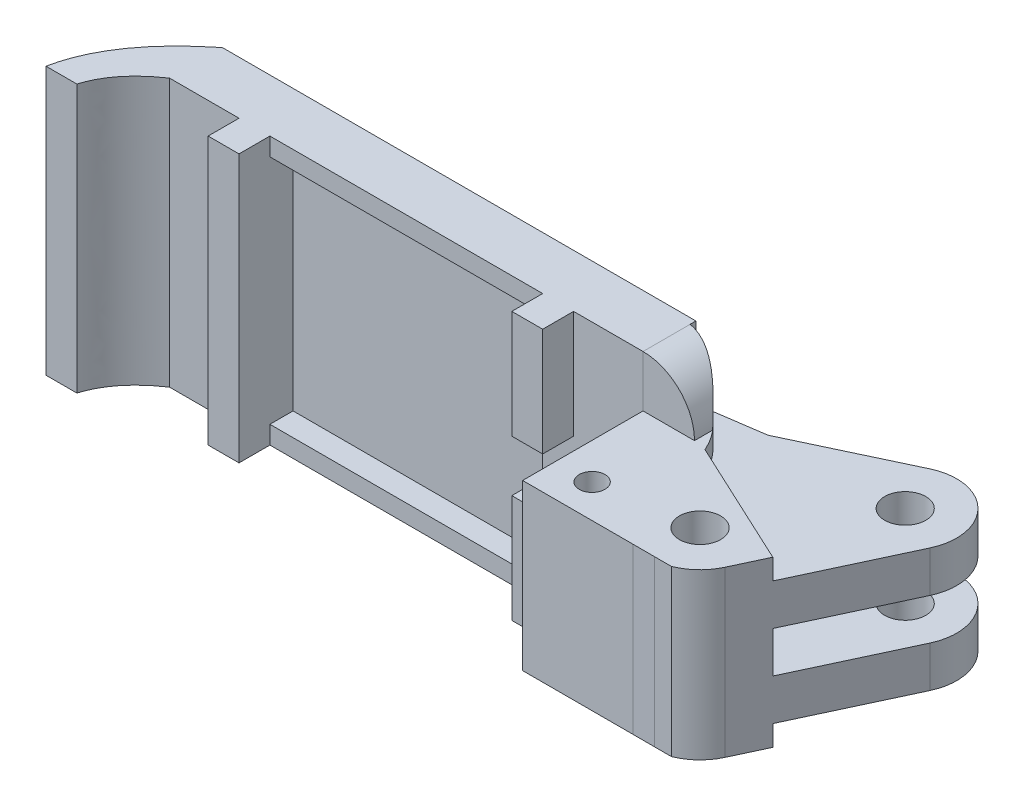
SolidWorks part; units mm, degrees
ref_plane "Front Plane" through (0, 0, 0) normal (0, 0, 1) x (1, 0, 0)
ref_plane "Top Plane" through (0, 0, 0) normal (0, 1, 0) x (1, 0, 0)
ref_plane "Right Plane" through (0, 0, 0) normal (1, 0, 0) x (0, 0, -1)
sketch "Sketch2" plane through (0, 0, 0) normal (0, 1, 0) x (1, 0, 0)
  line L0 (-8.5236, 1.406) -> (-14.8628, -12.1887)
  line L1 (-15.1825, 8.0439) -> (-25.8895, 3.0099)
  line L2 (-19.187, -14.7177) -> (-17.5368, -14.7177)
  line L3 (-19.187, -14.7177) -> (-21.2638, -14.713)
  line L4 (-25.8895, 3.0099) -> (-31.9894, 2.1239)
  line L5 (-31.9894, 2.1239) -> (-31.9894, 1.5541)
  line L6 (-31.9894, -14.713) -> (-21.2638, -14.713)
  arc A0 (-8.5236, 1.406) -> (-15.1825, 8.0439) centre (-13.0551, 3.519) ccw
  circle A1 centre (-19.3944, -10.0756) radius 2
  arc A2 (-17.5368, -14.7177) -> (-14.8628, -12.1887) centre (-19.3944, -10.0756) ccw
  arc A3 (-31.9894, -14.713) -> (-31.9894, 1.5541) centre (-33.2584, -6.5794) ccw
  circle A4 centre (-13.0551, 3.519) radius 2
  dimension "D1" = 15
extrude "Boss-Extrude1" add sketch "Sketch2" along normal blind 8 and the other way blind 8
sketch "Sketch3" plane through (0, -8, 0) normal (0, -1, 0) x (1, 0, 0)
  line L0 (-13.3837, 9.0166) -> (-36.0192, -1.5385)
  line L1 (-14.8628, 12.1887) -> (-8.5236, -1.406) construction
  line L3 (-25.8895, -3.0099) -> (-31.9894, -2.1239) construction
  line L4 (-15.1825, -8.0439) -> (-25.8895, -3.0099) construction
  line L5 (-25.8895, -3.0099) -> (-36.0192, -1.5385)
  line L6 (-15.1825, -8.0439) -> (-25.8895, -3.0099)
  line L7 (-13.3837, 9.0166) -> (-8.5236, -1.406)
  circle A0 centre (-19.3944, 10.0756) radius 2 construction
  arc A1 (-15.1825, -8.0439) -> (-8.5236, -1.406) centre (-13.0551, -3.519) ccw construction
  arc A2 (-15.1825, -8.0439) -> (-8.5236, -1.406) centre (-13.0551, -3.519) ccw
  dimension "D1" = 3.5
extrude "Cut-Extrude1" cut sketch "Sketch3" against normal blind 2
sketch "Sketch4" plane through (0, 8, 0) normal (0, 1, 0) x (1, 0, 0)
  line L0 (-13.3837, -9.0166) -> (-36.0192, 1.5385)
  line L1 (-14.8628, -12.1887) -> (-8.5236, 1.406) construction
  line L2 (-25.8895, 3.0099) -> (-31.9894, 2.1239) construction
  line L3 (-15.1825, 8.0439) -> (-25.8895, 3.0099) construction
  line L4 (-25.8895, 3.0099) -> (-36.0192, 1.5385)
  line L5 (-15.1825, 8.0439) -> (-25.8895, 3.0099)
  line L6 (-13.3837, -9.0166) -> (-8.5236, 1.406)
  circle A0 centre (-19.3944, -10.0756) radius 2 construction
  arc A1 (-8.5236, 1.406) -> (-15.1825, 8.0439) centre (-13.0551, 3.519) ccw construction
  arc A2 (-8.5236, 1.406) -> (-15.1825, 8.0439) centre (-13.0551, 3.519) ccw
  dimension "D1" = 3.5
extrude "Cut-Extrude2" cut sketch "Sketch4" against normal blind 2
sketch "Sketch7" plane through (0, -8, 0) normal (0, -1, 0) x (1, 0, 0)
  line L0 (-31.9894, -1.5541) -> (-31.9894, 14.713)
  arc A0 (-25.7246, 3.2619) -> (-31.9894, 14.713) centre (-33.2584, 6.5794) ccw construction
  arc A1 (-31.9894, -1.5541) -> (-25.7246, 3.2619) centre (-33.2584, 6.5794) ccw construction
  arc A2 (-25.7246, 3.2619) -> (-31.9894, 14.713) centre (-33.2584, 6.5794) ccw
  arc A3 (-31.9894, -1.5541) -> (-25.7246, 3.2619) centre (-33.2584, 6.5794) ccw
extrude "Boss-Extrude4" add sketch "Sketch7" against normal up to surface (16 mm away) up to face at (-20.1266, 8, 12.1609)
sketch "Sketch10" plane through (0, 0, 0) normal (0, 1, 0) x (1, 0, 0)
  line L0 (-25.8895, 3.0099) -> (-15.1825, 8.0439) construction
  line L1 (-8.5236, 1.406) -> (-13.3837, -9.0166) construction
  line L2 (-13.3837, -9.0166) -> (-25.7246, -3.2619) construction
  line L3 (-25.8895, 3.0099) -> (-15.1825, 8.0439)
  line L4 (-8.5236, 1.406) -> (-13.3837, -9.0166)
  line L5 (-13.3837, -9.0166) -> (-25.7246, -3.2619)
  line L6 (-31.9894, 2.1239) -> (-25.8895, 3.0099) construction
  line L7 (-31.9894, 2.1239) -> (-25.8895, 3.0099)
  line L8 (-31.9894, 2.1239) -> (-31.9894, 1.5541)
  arc A0 (-8.5236, 1.406) -> (-15.1825, 8.0439) centre (-13.0551, 3.519) ccw construction
  arc A1 (-8.5236, 1.406) -> (-15.1825, 8.0439) centre (-13.0551, 3.519) ccw
  arc A2 (-25.7246, -3.2619) -> (-31.9894, 1.5541) centre (-33.2584, -6.5794) ccw construction
  arc A3 (-25.7246, -3.2619) -> (-31.9894, 1.5541) centre (-33.2584, -6.5794) ccw
extrude "Cut-Extrude4" cut sketch "Sketch10" against normal blind 2 and the other way blind 2
sketch "Sketch12" plane through (0, 0, 0) normal (0, 1, 0) x (1, 0, 0)
  line L0 (-31.9894, 2.1239) -> (-77.9894, 2.1239)
  line L1 (-31.9894, -3.013) -> (-77.9894, -3.013)
  line L2 (-31.9894, -14.713) -> (-31.9894, 1.5541) construction
  line L3 (-77.9894, -3.013) -> (-77.9894, 2.1239)
  line L4 (-31.9894, 2.1239) -> (-31.9894, -3.013)
  dimension "D1" = 11.7
  dimension "D2" = 46
extrude "Boss-Extrude6" add sketch "Sketch12" along normal blind 13 and the other way blind 13
sketch "Sketch13" plane through (0, -8, 0) normal (0, -1, 0) x (1, 0, 0)
  line L0 (-31.9894, 8.213) -> (-24.9894, 14.713) construction
  line L1 (-31.9894, 14.713) -> (-24.9894, 14.713) construction
  line L2 (-31.9894, 14.713) -> (-31.9894, 8.213) construction
  line L3 (-31.9894, 8.213) -> (-24.9894, 8.213) construction
  line L4 (-24.9894, 14.713) -> (-24.9894, 8.213) construction
  line L5 (-24.9894, 8.213) -> (-31.9894, 14.713) construction
  circle A0 centre (-28.4894, 11.463) radius 1.25
  dimension "D3" = 2.5
  dimension "D1" = 7
  dimension "D2" = 6.5
extrude "Cut-Extrude5" cut sketch "Sketch13" against normal up to surface (16 mm away) up to face at (-23.0078, 8, 9.3602)
sketch "Sketch14" plane through (0, -13, 0) normal (0, -1, 0) x (1, 0, 0)
  line L0 (-31.9894, 13.013) -> (-84.9894, 13.013) construction
  line L1 (-31.9894, 14.713) -> (-31.9894, 3.013) construction
  line L2 (-77.9894, 3.013) -> (-31.9894, 3.013) construction
  line L3 (-77.9894, -2.1239) -> (-77.9894, 3.013) construction
  line L4 (-84.9894, 8.013) -> (12.0329, 8.013) construction
  line L5 (-81.9894, 8.013) -> (-84.9894, 8.013)
  line L6 (-77.9894, -2.1239) -> (-77.9894, 3.013)
  spline S0 degree 2 poles (-77.9894, 3.013) (-81.1124, 5.119) (-81.9894, 8.013) knots 0 0 0 0.561524 0.561524 0.561524
  spline S1 degree 2 poles (-77.9894, -2.1239) (-83.9294, 2.6173) (-84.9894, 8.013) knots 0 0 0 0.697154 0.697154 0.697154
  point P10 (-81.9894, 8.013)
  point P11 (-81.9894, 13.013)
  dimension "D1" = 10
  dimension "D2" = 7
  dimension "D3" = 5
  dimension "D4" = 3
extrude "Boss-Extrude7" add sketch "Sketch14" against normal up to surface (26 mm away) contours S0 L5 S1 L6 up to face at (-54.9894, 13, 0.4445)
sketch "Sketch15" plane through (0, 0, 3.013) normal (0, 0, 1) x (1, 0, 0)
  line L0 (-31.9894, -8) -> (-31.9894, 8) construction
  line L1 (-77.9894, -13) -> (-31.9894, -13) construction
  line L2 (-68.2394, -13) -> (-41.7394, -13) construction
  line L3 (-68.2394, -13) -> (-68.2394, 13) construction
  line L4 (-54.9894, -13) -> (-54.9894, 13) construction
  line L5 (-68.2394, 13) -> (-41.7394, 13) construction
  line L6 (-41.7394, -13) -> (-41.7394, 13) construction
  line L7 (-77.9894, 13) -> (-31.9894, 13) construction
  line L8 (-68.2394, -13) -> (-41.7394, 13) construction
  line L9 (-41.7394, -13) -> (-68.2394, 13) construction
  line L11 (-41.7394, -13) -> (-38.7394, -13)
  line L12 (-41.7394, -13) -> (-41.7394, 13)
  line L13 (-41.7394, 13) -> (-38.7394, 13)
  line L14 (-38.7394, -13) -> (-38.7394, 13)
  line L15 (-71.2394, -13) -> (-68.2394, -13)
  line L16 (-71.2394, -13) -> (-71.2394, 13)
  line L17 (-71.2394, 13) -> (-68.2394, 13)
  line L18 (-68.2394, -13) -> (-68.2394, 13)
  point P14 (-54.9894, 0)
  dimension "D1" = 23
  dimension "D2" = 26.5
  dimension "D3" = 3
  dimension "D4" = 3
extrude "Boss-Extrude8" add sketch "Sketch15" along normal blind 3
sketch "Sketch20" plane through (-31.9894, 0, 0) normal (-1, 0, 0) x (0, 0, 1)
  line L0 (-1.5541, 2) -> (3.2619, 2) construction
  line L1 (1.7713, 2) -> (4.2713, 2)
  line L2 (1.7713, 2) -> (1.7713, -2)
  line L3 (1.7713, -2) -> (4.2713, -2)
  line L4 (4.2713, 2) -> (4.2713, -2)
  line L5 (9.0166, -2) -> (-1.406, -2) construction
  line L6 (3.2619, -2) -> (-1.5541, -2) construction
  dimension "D1" = 2.5
extrude "Cut-Extrude8" cut sketch "Sketch20" against normal through all
sketch "Sketch21" plane through (0, 0, -2.1239) normal (0, 0, -1) x (-1, 0, 0)
  line L0 (31.9894, 6) -> (31.9894, 13) construction
  line L1 (31.9894, 8) -> (25.7246, 8) construction
  line L2 (26.9894, 8) -> (31.9894, 8)
  line L3 (31.9894, 8) -> (31.9894, 13)
  arc A0 (31.9894, 13) -> (26.9894, 8) centre (31.9894, 8) ccw
extrude "Boss-Extrude9" add sketch "Sketch21" against normal blind 5.14
sketch "Sketch22" plane through (0, 13, 0) normal (0, 1, 0) x (1, 0, 0)
  line L0 (-31.9894, 1.5541) -> (-31.9894, 2.1239)
  line L1 (-31.9894, 2.1239) -> (-26.9894, 2.1239)
  line L2 (-26.9894, 2.1239) -> (-26.9894, -1.2443)
  arc A1 (-26.9894, -1.2443) -> (-31.9894, 1.5541) centre (-33.2584, -6.5794) ccw construction
  arc A2 (-26.9894, -1.2443) -> (-31.9894, 1.5541) centre (-33.2584, -6.5794) ccw
  arc A3 (-26.9894, -1.2443) -> (-31.9894, 1.5541) centre (-33.2584, -6.5794) ccw
  line M1 (-31.9894, -3.013) -> (-31.9894, 2.1239)
extrude "Cut-Extrude9" cut sketch "Sketch22" against normal blind 5.14 contours A2 L2 L1 M1 region at (-28.7736, 13, -1.1343)
sketch "Sketch23" plane through (0, 0, -2.1239) normal (0, 0, -1) x (-1, 0, 0)
  line L0 (25.7246, -8) -> (31.9894, -8) construction
  line L1 (31.9894, -8) -> (31.9894, -13)
  line L2 (31.9894, -8) -> (26.9894, -8)
  arc A0 (31.9894, -13) -> (26.9894, -8) centre (31.9894, -8) cw
extrude "Boss-Extrude10" add sketch "Sketch23" against normal blind 5.14
sketch "Sketch24" plane through (0, -13, 0) normal (0, -1, 0) x (1, 0, 0)
  line L2 (-31.9894, 3.0161) -> (-26.9894, 3.0161) construction
  line L3 (-25.8377, 3.0161) -> (-31.9894, 3.0161) construction
  line L4 (-31.9894, 3.0161) -> (-31.9894, -1.5541) construction
  line L5 (-31.9894, -1.5541) -> (-31.9894, -2.1239)
  line L6 (-31.9894, -2.1239) -> (-26.9894, -2.1239) construction
  line L7 (-31.9894, 3.013) -> (-31.9894, -2.1239) construction
  line L8 (-31.9894, -2.1239) -> (-25.8377, -2.1239)
  line L9 (-25.8377, -2.1239) -> (-25.8377, 3.0161)
  arc A0 (-31.9894, -1.5541) -> (-26.9894, 1.2443) centre (-33.2584, 6.5794) ccw construction
  arc A1 (-31.9894, -1.5541) -> (-26.9894, 1.2443) centre (-33.2584, 6.5794) ccw
  arc A2 (-26.9894, 1.2443) -> (-25.7246, 3.2619) centre (-33.2584, 6.5794) ccw construction
  arc A3 (-26.9894, 1.2443) -> (-25.8377, 3.0161) centre (-33.2584, 6.5794) ccw
extrude "Cut-Extrude10" cut sketch "Sketch24" against normal blind 5.14
sketch "Sketch25" plane through (0, 0, 3.013) normal (0, 0, 1) x (1, 0, 0)
  line L0 (-68.2394, -11.25) -> (-41.7394, -11.25)
  line L1 (-68.2394, -13) -> (-68.2394, 13) construction
  line L2 (-41.7394, 13) -> (-41.7394, -13) construction
  line L3 (-41.7394, -11.25) -> (-41.7394, 11.25)
  line L4 (-41.7394, 11.25) -> (-68.2394, 11.25)
  line L5 (-68.2394, 11.25) -> (-68.2394, -11.25)
  line L6 (-68.2394, -13) -> (-41.7394, -13) construction
  line L7 (-68.2394, 13) -> (-41.7394, 13) construction
  dimension "D1" = 1.75
  dimension "D2" = 1.75
extrude "Cut-Extrude11" cut sketch "Sketch25" against normal blind 2.25
sketch "Sketch26" plane through (0, 0, 6.013) normal (0, 0, 1) x (1, 0, 0)
  line L0 (-41.7394, 13) -> (-41.7394, -13) construction
  line L1 (-41.7394, -2.5) -> (-38.7394, -2.5)
  line L2 (-41.7394, -2.5) -> (-41.7394, 2.5)
  line L3 (-41.7394, 2.5) -> (-38.7394, 2.5)
  line L4 (-38.7394, -2.5) -> (-38.7394, 2.5)
  line L5 (-38.7394, -13) -> (-38.7394, 13) construction
  line L6 (-40.2394, -13) -> (-40.2394, -2.5) construction
  line L7 (-41.7394, -13) -> (-38.7394, -13) construction
  line L8 (-40.2394, 2.5) -> (-40.2394, 13) construction
  line L9 (-38.7394, 13) -> (-41.7394, 13) construction
  dimension "D1" = 5
extrude "Cut-Extrude12" cut sketch "Sketch26" against normal up to surface (3 mm away) up to face at (-54.9894, -12.125, 3.013)
